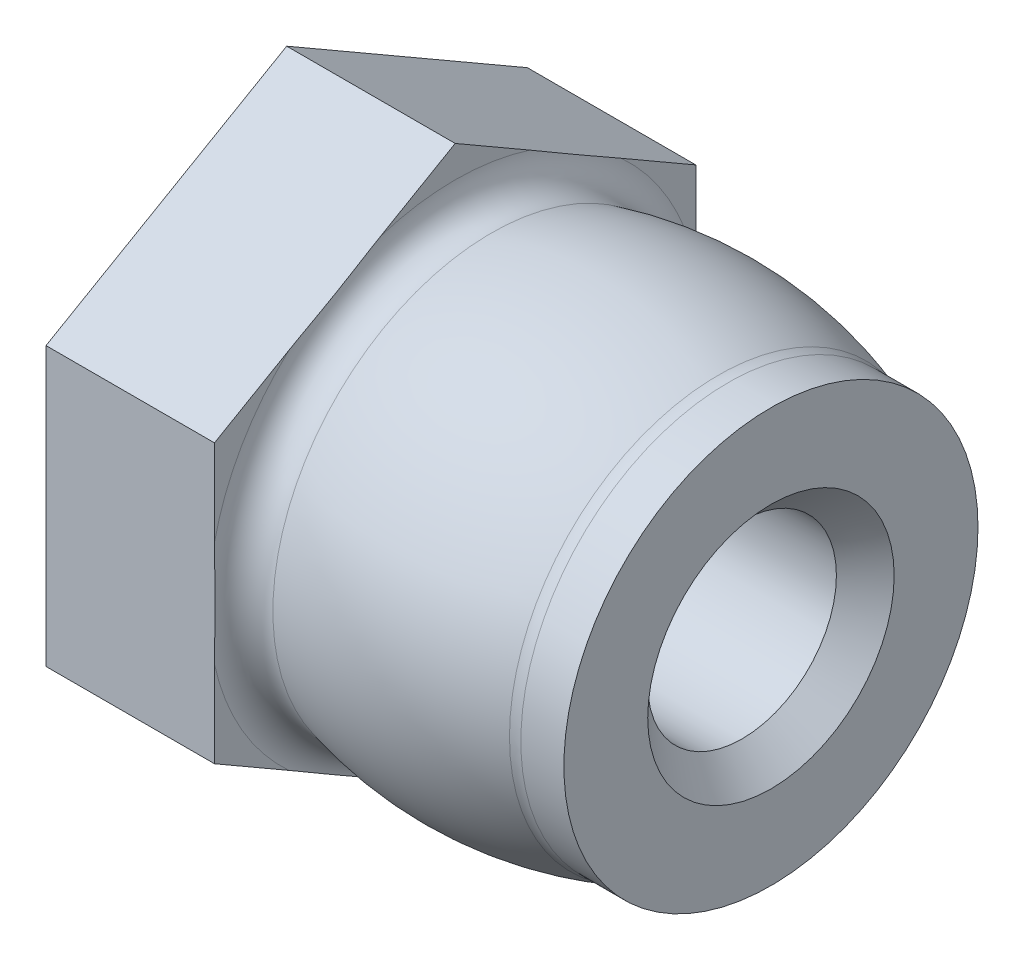
SolidWorks part; units mm, degrees
ref_plane "Front" through (0, 0, 0) normal (0, 0, 1) x (1, 0, 0)
ref_plane "Top" through (0, 0, 0) normal (0, 1, 0) x (1, 0, 0)
ref_plane "Right" through (0, 0, 0) normal (1, 0, 0) x (0, 0, -1)
sketch "Sketch1" plane through (0, 0, 0) normal (0, 0, 1) x (1, 0, 0)
  line L0 (0, -52.2509) -> (0, 2560.2944) construction
  line L1 (-52.2509, 0) -> (2560.2944, 0) construction
  line L2 (0, 2.7314) -> (0, 1.2446)
  line L3 (0, 1.2446) -> (-5.7531, 1.2446)
  line L4 (-5.7531, 1.2446) -> (-5.7531, 3.175)
  line L5 (-5.7531, 3.175) -> (-3.5306, 3.175)
  line L6 (-3.5306, 3.175) -> (-3.5306, 2.7314)
  arc A0 (0, 2.7314) -> (-3.5306, 2.7314) centre (-1.7653, -2.032) ccw
  dimension "D6" = 5.08
  dimension "D1" = 6.35
  dimension "D2" = 2.4892
  dimension "D3" = 2.2225
  dimension "D4" = 3.9878
  dimension "D5" = 5.4628
revolve "Revolve1" add sketch "Sketch1" angle 360 about L1
sketch "Sketch3" plane through (-5.7531, 0, 0) normal (-1, 0, 0) x (0, 0, 1)
  line L1 (3.175, 1.8331) -> (0, 3.6662)
  line L2 (0, 3.6662) -> (-3.175, 1.8331)
  line L3 (-3.175, 1.8331) -> (-3.175, -1.8331)
  line L4 (-3.175, -1.8331) -> (0, -3.6662)
  line L5 (0, -3.6662) -> (3.175, -1.8331)
  line L6 (3.175, -1.8331) -> (3.175, 1.8331)
  circle A0 centre (0, 0) radius 3.175 construction
  circle A1 centre (0, 0) radius 3.175
  circle A2 centre (0, 0) radius 3.175
  circle M9 centre (0, 0) radius 3.175
  dimension "D1" = 0
extrude "Boss-Extrude1" add sketch "Sketch3" against normal up to surface (2.2225 mm away) contours L1 L2 M9 | L6 L1 M9 | L5 L6 M9 | L4 L5 M9 | L3 L4 M9 | L2 L3 M9 region at (-5.7531, 1.6408, 2.8419) region at (-5.7531, 3.2816, 0) region at (-5.7531, -1.6408, 2.8419) region at (-5.7531, 1.6408, -2.8419) region at (-5.7531, -3.2816, 0) region at (-5.7531, -1.6408, -2.8419) up to face at (-3.5306, 0, 3.175)
sketch "Sketch4" plane through (0, 0, 0) normal (1, 0, 0) x (0, 0, -1)
  circle A0 centre (0, 0) radius 1.2446
  circle A1 centre (0, 0) radius 2.7314
  circle A2 centre (0, 0) radius 2.7314
  circle A3 centre (0, 0) radius 1.2446
extrude "Boss-Extrude2" add sketch "Sketch4" along normal blind 0.635
fillet "Fillet1" radius 0.381 1 edges at (-3.5306, 0, 2.7314) type face fillet first side face at (-3.5306, 0, 0) second side face at (-3.5306, 0, 2.7314)
fillet "Fillet2" radius 0.381 1 edges at (0, 0, -2.7314)
chamfer "Chamfer1" distance 0.381 1 edges at (0.635, 0, -1.2446)
